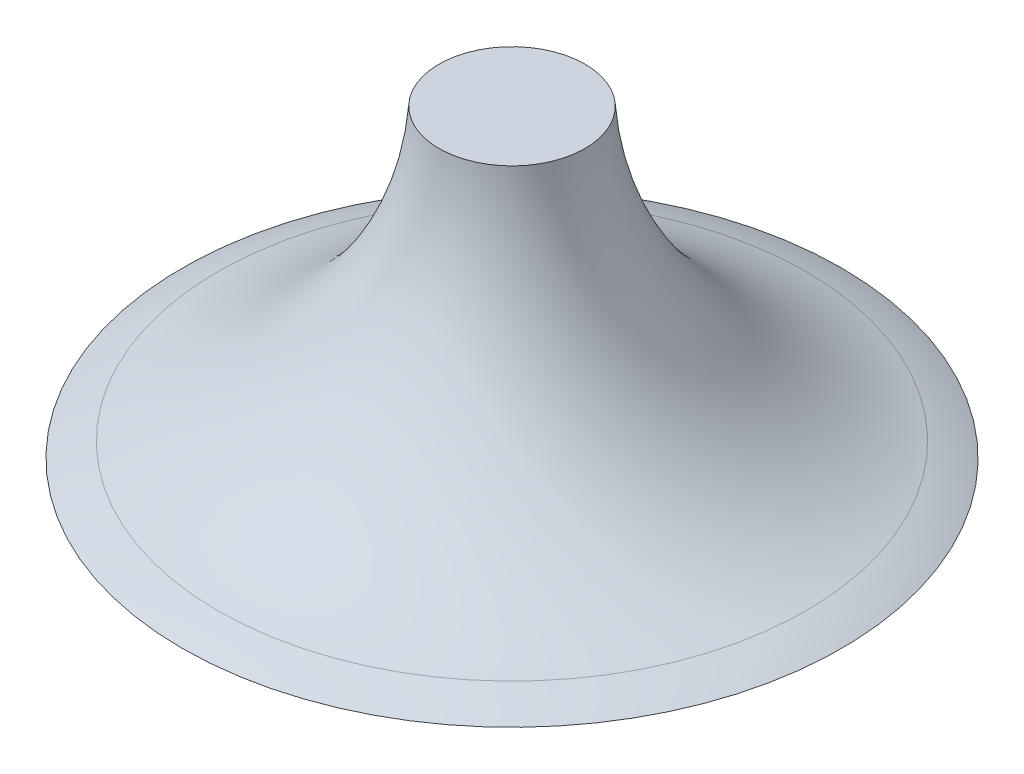
SolidWorks part; units mm, degrees
material "PS HI"
ref_plane "Front Plane" through (0, 0, 0) normal (0, 0, 1) x (1, 0, 0)
ref_plane "Top Plane" through (0, 0, 0) normal (0, 1, 0) x (1, 0, 0)
ref_plane "Right Plane" through (0, 0, 0) normal (1, 0, 0) x (0, 0, -1)
sketch "Sketch1" plane through (0, 0, 0) normal (1, 0, 0) x (0, 0, -1)
  line L0 (0, 0) -> (5.5407, 11.8821)
  line L1 (0, 0) -> (0, 40)
  line L2 (0, 55) -> (0, -55) construction
  line L3 (0, 40) -> (5.5407, 40)
  line L4 (5.5407, 40) -> (5.5407, 19.3821)
  line L5 (5.5407, 19.3821) -> (25, 19.3821)
  line L6 (25, 19.3821) -> (25, 16.8821)
  line L7 (25, 16.8821) -> (5.5407, 16.8821)
  line L8 (5.5407, 16.8821) -> (5.5407, 11.8821)
  dimension "D1" = 40
  dimension "D2" = 25
  dimension "D3" = 25
  dimension "D4" = 2.5
  dimension "D5" = 20.6179
  dimension "D6" = 5
revolve "Revolve1" add sketch "Sketch1" angle 360 about L1 other way angle 360
fillet "Fillet1" radius 25 1 edges at (0, 16.8821, -5.5407)
fillet "Fillet4" radius 25 1 edges at (0, 11.8821, -5.5407)
fillet "Fillet5" radius 25 1 edges at (0, 19.3821, -25)
fillet "Fillet9" radius 25 1 edges at (0, 19.3821, -5.5407)
ref_plane "Plane1" through (0, 40, 0) normal (0, 1, 0) x (1, 0, 0)
